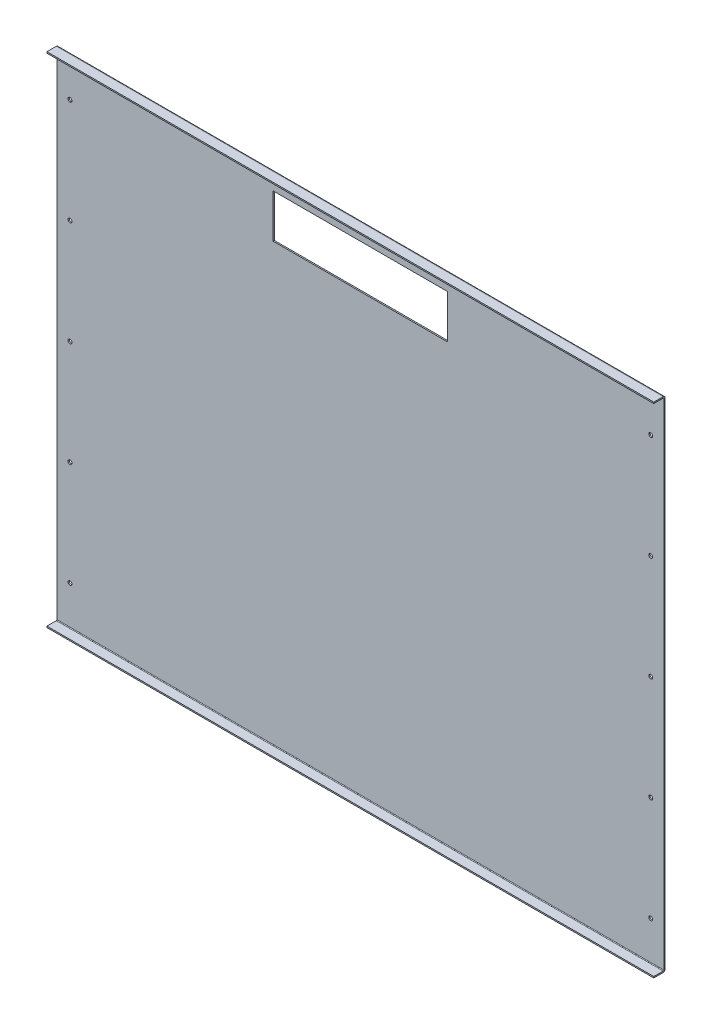
SolidWorks part; units mm, degrees
note: The reader was unsure of these and kept them because the rebuilt part matched: flange length of "Ребро-кромка1".
ref_plane "Спереди" through (0, 0, 0) normal (0, 0, 1) x (1, 0, 0)
ref_plane "Сверху" through (0, 0, 0) normal (0, 1, 0) x (1, 0, 0)
ref_plane "Справа" through (0, 0, 0) normal (1, 0, 0) x (0, 0, -1)
sketch "Эскиз1" plane through (0, 0, 0) normal (0, 0, 1) x (1, 0, 0)
  line L1 (-348, -286) -> (348, -286)
  line L2 (-348, -286) -> (-348, 286)
  line L3 (-348, 286) -> (348, 286)
  line L4 (348, -286) -> (348, 286)
  line L5 (-348, -286) -> (348, 286) construction
  line L6 (-348, 286) -> (348, -286) construction
  point P0 (0, 0)
  dimension "D1" = 572
  dimension "D2" = 696
base flange "Базовая кромка1" sketch "Эскиз1" thickness 1.5 reverse thickness direction no parameters "D1"=0.7366
edge flange "Ребро-кромка1" sketch "Эскиз6" flange profiles "Эскиз6", "Эскиз7" flange angle 90 flange length 13 flange position material inside bend radius 0.7366 thickness 1.5 relief rectangular parameters "D6"=10, "D8"=1
sketch "Эскиз6" plane through (0, 286, 0) normal (0, 1, 0) x (-1, 0, 0)
  line L2 (-348, 0) -> (-348, 11.5)
  line L3 (-348, 11.5) -> (348, 11.5)
  line L4 (348, 11.5) -> (348, 0)
  line L5 (-348, 0) -> (348, 0) construction
  line L6 (-348, 0) -> (348, 0)
sketch "Эскиз7" plane through (0, -286, 0) normal (0, -1, 0) x (1, 0, 0)
  line L1 (-348, 0) -> (348, 0) construction
  line L2 (348, 0) -> (348, 11.5)
  line L3 (348, 11.5) -> (-348, 11.5)
  line L4 (-348, 11.5) -> (-348, 0)
  line L5 (-348, 0) -> (348, 0)
bend "EdgeBend1" bend radius 0.7366 bend angle 90 parameters "D5"=1
bend "EdgeBend2" bend radius 0.7366 bend angle 90 parameters "D5"=2
sketch "Эскиз8" plane through (0, 0, 0) normal (0, 0, 1) x (1, 0, 0)
  line L0 (0, 0) -> (0, 110.0356) construction
  line L1 (348, -283.7634) -> (348, 283.7634) construction
  circle A0 centre (333, 0) radius 2.25
  circle A1 centre (-333, 0) radius 2.25
  dimension "D1" = 4.5
  dimension "D2" = 15
extrude "Вырез-Вытянуть1" cut sketch "Эскиз8" against normal blind 10
pattern_linear "Линейный массив1" count 3 spacing 120 along (0, -1, 0) count 3 spacing 120 along (0, 1, 0) of "Вырез-Вытянуть1"
sketch "Эскиз9" plane through (0, 0, 0) normal (0, 0, 1) x (1, 0, 0)
  line L0 (-348, 286) -> (348, 286) construction
  line L1 (-100, 266) -> (100, 266)
  line L2 (-100, 266) -> (-100, 216)
  line L3 (-100, 216) -> (100, 216)
  line L4 (100, 266) -> (100, 216)
  line L5 (-100, 266) -> (100, 216) construction
  line L6 (-100, 216) -> (100, 266) construction
  point P0 (0, 241)
  dimension "D1" = 200
  dimension "D2" = 50
  dimension "20" = 20
extrude "Вырез-Вытянуть2" cut sketch "Эскиз9" against normal blind 10
sketch "Сгиб-Линии1" [suppressed] plane through (0, 0, 0) normal (0, 1, 0) x (1, 0, 0)
sketch "Граничная рамка1" [suppressed] plane through (0, 0, 0) normal (0, 1, 0) x (1, 0, 0)
sheet metal parameters "Листовой металл3" thickness 1.5 parameters "D1"=0.7366
flat pattern "Развертка3" [suppressed]
sketch "Сгиб-Линии2" plane through (0, 0, 0) normal (0, 1, 0) x (1, 0, 0)
sketch "Граничная рамка2" [suppressed] plane through (0, 0, 0) normal (0, 1, 0) x (1, 0, 0)
sheet metal parameters "Листовой металл15" thickness 1.5 parameters "D1"=0.7366
flat pattern "Развертка3" [suppressed]
sketch "Сгиб-Линии2" plane through (0, 0, 0) normal (0, 1, 0) x (1, 0, 0)
sketch "Граничная рамка2" [suppressed] plane through (0, 0, 0) normal (0, 1, 0) x (1, 0, 0)
bend of the flat pattern "Плоское состояние-<EdgeBend1>1"
bend of the flat pattern "Плоское состояние-<EdgeBend2>1"
sheet metal parameters "Листовой металл16" thickness 1.5 parameters "D1"=0.7366
flat pattern "Развертка3" [suppressed]
sketch "Сгиб-Линии2" plane through (0, 0, 0) normal (0, 1, 0) x (1, 0, 0)
sketch "Граничная рамка2" [suppressed] plane through (0, 0, 0) normal (0, 1, 0) x (1, 0, 0)
bend of the flat pattern "Плоское состояние-<EdgeBend1>1"
bend of the flat pattern "Плоское состояние-<EdgeBend2>1"
sheet metal parameters "Листовой металл17" thickness 1.5 parameters "D1"=0.7366
flat pattern "Развертка3" [suppressed]
sketch "Сгиб-Линии2" plane through (0, 0, 0) normal (0, 1, 0) x (1, 0, 0)
sketch "Граничная рамка2" [suppressed] plane through (0, 0, 0) normal (0, 1, 0) x (1, 0, 0)
bend of the flat pattern "Плоское состояние-<EdgeBend1>1"
bend of the flat pattern "Плоское состояние-<EdgeBend2>1"
sheet metal parameters "Листовой металл18" thickness 1.5 parameters "D1"=0.7366
flat pattern "Развертка3"
sketch "Сгиб-Линии2" plane through (0, 0, 0) normal (0, 0, 1) x (1, 0, 0)
  line L0 (-348, -284.8132) -> (348, -284.8132) construction
  line L1 (348, 284.8132) -> (-348, 284.8132) construction
  line L2 (-348, -284.8132) -> (348, -284.8132) construction
  line L3 (348, 284.8132) -> (-348, 284.8132) construction
sketch3d "Граничная рамка2" [suppressed]
  line L0 (-348, -296.6263, 0) -> (348, -296.6263, 0) construction
  line L1 (-348, 296.6263, 0) -> (348, 296.6263, 0) construction
  line L2 (-348, -296.6263, 0) -> (-348, 296.6263, 0) construction
  line L3 (348, -296.6263, 0) -> (348, 296.6263, 0) construction
bend of the flat pattern "Плоское состояние-<EdgeBend1>1"
bend of the flat pattern "Плоское состояние-<EdgeBend2>1"
